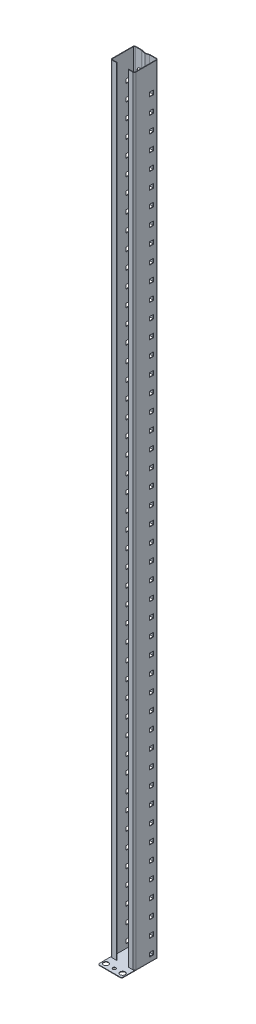
SolidWorks part; units mm, degrees
material "ASTM A36 Steel"
ref_plane "Front Plane" through (0, 0, 0) normal (0, 0, 1) x (1, 0, 0)
ref_plane "Top Plane" through (0, 0, 0) normal (0, 1, 0) x (1, 0, 0)
ref_plane "Right Plane" through (0, 0, 0) normal (1, 0, 0) x (0, 0, -1)
sketch "Sketch1" plane through (0, 0, 0) normal (0, 1, 0) x (1, 0, 0)
  line L0 (-11.3032, 37.1454) -> (-1.2271, 34.4585)
  line L1 (-32.5437, -37.3063) -> (-18.2562, -37.3063)
  line L2 (-37.3062, -32.5437) -> (-37.3062, 32.5437)
  line L3 (-32.5437, 37.3062) -> (-12.5303, 37.3062)
  line L4 (37.3062, -32.5437) -> (37.3062, 32.5437)
  line L5 (-37.3062, -37.3063) -> (37.3062, 37.3062) construction
  line L6 (-37.3062, 37.3062) -> (37.3062, -37.3063) construction
  line L7 (1.2271, 34.4585) -> (11.3032, 37.1454)
  line L8 (0, 0) -> (0, 50000) construction
  line L9 (0, 0) -> (50000, 0) construction
  line L10 (-18.2562, -37.3063) -> (-18.2562, -35.7188)
  line L11 (18.2562, -37.3063) -> (18.2562, -35.7188)
  line L12 (18.2562, -37.3063) -> (32.5437, -37.3063)
  line L13 (12.5303, 37.3062) -> (32.5437, 37.3062)
  line L14 (-32.5437, -35.7188) -> (-19.8437, -35.7188) construction
  line L15 (-32.5437, -35.7188) -> (-18.2562, -35.7188)
  line L16 (-35.7188, -32.5437) -> (-35.7188, 32.5437)
  line L17 (-32.5437, 35.7187) -> (-12.5303, 35.7187)
  line L18 (-11.7123, 35.6115) -> (-1.6362, 32.9246)
  line L19 (1.6362, 32.9246) -> (11.7123, 35.6115)
  line L20 (12.5303, 35.7187) -> (32.5437, 35.7187)
  line L21 (35.7188, -32.5437) -> (35.7188, 32.5437)
  line L22 (18.2562, -35.7188) -> (32.5437, -35.7188)
  line L23 (-18.2562, -37.3063) -> (-18.2562, -34.5888) construction
  line L24 (-19.8437, -35.7188) -> (-19.8437, -34.5888) construction
  line L25 (19.8437, -35.7188) -> (19.8437, -34.5888) construction
  line L26 (18.2562, -37.3063) -> (18.2562, -34.5888) construction
  line L27 (19.8437, -35.7188) -> (32.5437, -35.7188) construction
  arc A0 (-37.3062, -32.5437) -> (-32.5437, -37.3063) centre (-32.5437, -32.5438) ccw
  arc A1 (37.3062, -32.5437) -> (32.5437, -37.3063) centre (32.5437, -32.5438) cw
  arc A2 (37.3062, 32.5437) -> (32.5437, 37.3062) centre (32.5437, 32.5437) ccw
  arc A3 (-32.5437, 37.3062) -> (-37.3062, 32.5437) centre (-32.5437, 32.5437) ccw
  arc A4 (12.5303, 37.3062) -> (11.3032, 37.1454) centre (12.5303, 32.5437) ccw
  arc A5 (1.2271, 34.4585) -> (-1.2271, 34.4585) centre (0, 39.0602) cw
  arc A6 (-11.3032, 37.1454) -> (-12.5303, 37.3062) centre (-12.5303, 32.5437) ccw
  arc A7 (-35.7188, -32.5437) -> (-32.5437, -35.7188) centre (-32.5437, -32.5438) ccw
  arc A8 (-32.5437, 35.7187) -> (-35.7188, 32.5437) centre (-32.5437, 32.5437) ccw
  arc A9 (-11.7123, 35.6115) -> (-12.5303, 35.7187) centre (-12.5303, 32.5437) ccw
  arc A10 (1.6362, 32.9246) -> (-1.6362, 32.9246) centre (0, 39.0602) cw
  arc A11 (12.5303, 35.7187) -> (11.7123, 35.6115) centre (12.5303, 32.5437) ccw
  arc A12 (35.7188, 32.5437) -> (32.5437, 35.7187) centre (32.5437, 32.5437) ccw
  arc A13 (35.7188, -32.5437) -> (32.5437, -35.7188) centre (32.5437, -32.5438) cw
  point P0 (0, 0)
  point P31 (11.9062, 37.3062)
  point P34 (0, 34.1312)
  point P37 (-11.9062, 37.3062)
  dimension "D8" = 4.7625
  dimension "D9" = 4.7625
  dimension "D1" = 74.6125
  dimension "D2" = 74.6125
  dimension "D3" = 3.175
  dimension "D4" = 25.4
  dimension "D5" = 25.4
  dimension "D6" = 19.05
  dimension "D7" = 19.05
  dimension "D10" = 1.5875
extrude "Boss-Extrude1" add sketch "Sketch1" along normal blind 2438.4
sketch "Sketch2" plane through (37.3062, 0, 0) normal (1, 0, 0) x (0, 0, -1)
  line L0 (37.3062, 2438.4) -> (37.3062, 0) construction
  line L1 (23.0187, 12.7) -> (10.3187, 12.7)
  line L2 (23.0187, 12.7) -> (23.0187, 25.4)
  line L3 (23.0187, 25.4) -> (10.3187, 25.4)
  line L4 (10.3187, 12.7) -> (10.3187, 25.4)
  line L5 (23.0187, 12.7) -> (10.3187, 25.4) construction
  line L6 (23.0187, 25.4) -> (10.3187, 12.7) construction
  line L7 (-32.5437, 0) -> (32.5437, 0) construction
  point P0 (16.6687, 19.05)
  dimension "D1" = 12.7
  dimension "D2" = 12.7
  dimension "D3" = 14.2875
  dimension "D4" = 25.4
extrude "Cut-Extrude1" cut sketch "Sketch2" against normal through all
sketch "Sketch3" plane through (0, 0, -37.3062) normal (0, 0, -1) x (-1, 0, 0)
  line L0 (17.4625, 50.8) -> (36.7087, 50.8) construction
  line L1 (17.4625, 25.4) -> (35.1932, 25.4) construction
  line L2 (17.4625, 30.1625) -> (17.4625, 41.275) construction
  line L3 (0, 0) -> (0, -50000) construction
  line L4 (32.5437, 0) -> (18.2562, 0) construction
  line L5 (21.7655, 28.1214) -> (26.0684, 37.1929)
  line L6 (12.7, 30.1625) -> (12.7, 33.0261)
  line L7 (-12.7, 30.1625) -> (-12.7, 33.0261)
  line L8 (-21.7655, 28.1214) -> (-26.0684, 37.1929)
  arc A0 (26.0684, 37.1929) -> (12.7, 33.0261) centre (17.4625, 41.275) ccw
  arc A1 (12.7, 30.1625) -> (21.7655, 28.1214) centre (17.4625, 30.1625) ccw
  arc A2 (-12.7, 30.1625) -> (-21.7655, 28.1214) centre (-17.4625, 30.1625) cw
  arc A3 (-26.0684, 37.1929) -> (-12.7, 33.0261) centre (-17.4625, 41.275) cw
  dimension "D1" = 19.05
  dimension "D2" = 9.525
  dimension "D3" = 25.4
  dimension "D4" = 17.4625
  dimension "D5" = 50.8
extrude "Cut-Extrude2" cut sketch "Sketch3" against normal blind 25.4
pattern_linear "LPattern1" count 47 spacing 50.8 along (0, 1, 0) of "Cut-Extrude2", "Cut-Extrude1"
sketch "Sketch4" plane through (0, 0, 0) normal (0, -1, 0) x (1, 0, 0)
  line L0 (0, 0) -> (0, -50000) construction
  line L1 (0, 0) -> (50000, 0) construction
  line L2 (22.537, -37.3062) -> (-49977.463, -37.3062) construction
  line L3 (32.5437, -37.3062) -> (12.5303, -37.3062) construction
  line L4 (-12.5303, -37.3062) -> (-32.5437, -37.3062) construction
  line L5 (-37.3062, 0) -> (-37.3062, -50000) construction
  line L6 (-37.3062, -32.5437) -> (-37.3062, 32.5437) construction
  line L7 (37.3062, 0) -> (37.3062, -50000) construction
  line L8 (37.3062, 32.5437) -> (37.3062, -32.5437) construction
  line L9 (0, 62.7063) -> (50000, 62.7063) construction
  line L10 (-32.5438, -37.3063) -> (32.5437, -37.3063)
  line L11 (-37.3063, -32.5438) -> (-37.3062, 72.2312)
  line L12 (-32.5437, 76.9938) -> (32.5437, 76.9938)
  line L13 (37.3062, -32.5438) -> (37.3063, 72.2312)
  line L14 (0, -23.0187) -> (50000, -23.0187) construction
  circle A0 centre (0, 62.7063) radius 4.7625
  circle A1 centre (-26.1938, 62.7063) radius 7.9375
  circle A2 centre (26.1937, 62.7063) radius 7.9375
  circle A3 centre (0, -23.0188) radius 4.7625
  circle A4 centre (26.1937, -23.0188) radius 7.9375
  circle A5 centre (-26.1938, -23.0188) radius 7.9375
  arc A6 (-37.3063, -32.5438) -> (-32.5438, -37.3063) centre (-32.5438, -32.5438) ccw
  arc A7 (37.3062, -32.5438) -> (32.5437, -37.3063) centre (32.5437, -32.5438) cw
  arc A8 (37.3063, 72.2312) -> (32.5437, 76.9938) centre (32.5438, 72.2313) ccw
  arc A9 (-32.5437, 76.9938) -> (-37.3062, 72.2312) centre (-32.5437, 72.2313) ccw
  point P9 (22.537, -37.3062)
  point P12 (-22.537, -37.3062)
  point P17 (-37.3062, 0)
  point P22 (37.3062, 0)
  point P47 (-37.3063, -37.3063)
  point P52 (37.3063, 76.9938)
  point P55 (-37.3062, 76.9938)
  dimension "D6" = 15.875
  dimension "D7" = 9.525
  dimension "D8" = 4.7625
  dimension "D1" = 114.3
  dimension "D2" = 14.2875
  dimension "D3" = 14.2875
  dimension "D4" = 52.3875
  dimension "D5" = 26.1937
extrude "Boss-Extrude2" add sketch "Sketch4" along normal blind 1.5875 separate body
